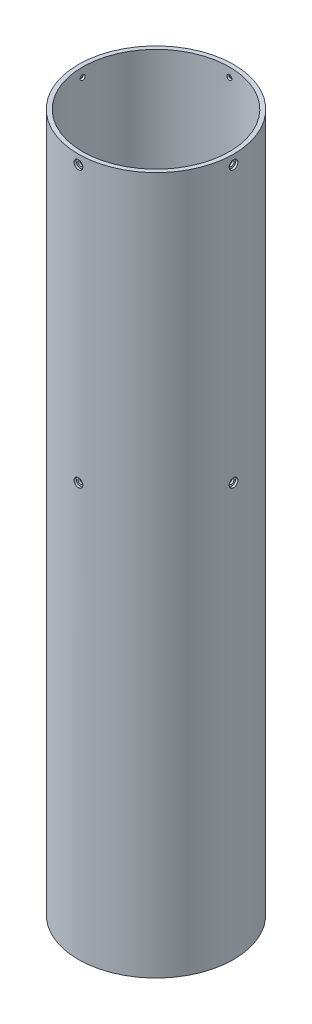
SolidWorks part; units mm, degrees
material "Hexcel AS4C (3000 Filaments)"
ref_plane "Front Plane" through (0, 0, 0) normal (0, 0, 1) x (1, 0, 0)
ref_plane "Top Plane" through (0, 0, 0) normal (0, 1, 0) x (1, 0, 0)
ref_plane "Right Plane" through (0, 0, 0) normal (1, 0, 0) x (0, 0, -1)
sketch "Sketch1" plane through (0, 0, 0) normal (0, 1, 0) x (1, 0, 0)
  circle A0 centre (0, 0) radius 50.8
  dimension "D1" = 101.6
extrude "Body Extrusion" add sketch "Sketch1" along normal blind 482.6 thin thin type one direction wall 2.921
ref_plane "Plane1" through (0, 0, 53.721) normal (0, 0, 1) x (1, 0, 0)
sketch "Sketch2" plane through (0, 0, 53.721) normal (0, 0, 1) x (1, 0, 0)
  line L0 (0, 482.6) -> (0, 0) construction
  line L1 (53.721, 482.6) -> (-53.721, 482.6) construction
  line L3 (50.8, 482.6) -> (-50.8, 482.6) construction
  circle A0 centre (0, 476.25) radius 1.7526
  dimension "D1" = 3.5052
  dimension "D2" = 6.35
extrude "Upper Bulkhead Holes" cut sketch "Sketch2" against normal up to next
pattern_circular "Upper Bulkhead Hole Pattern" count 4 over 360 about axis through (0, 482.6, 0) along (0, -1, 0) of "Upper Bulkhead Holes"
sketch "Sketch3" plane through (0, 0, 53.721) normal (0, 0, 1) x (1, 0, 0)
  line L0 (0, 482.6) -> (0, 0) construction
  line L1 (53.721, 482.6) -> (-53.721, 482.6) construction
  line L2 (50.8, 482.6) -> (-50.8, 482.6) construction
  circle A0 centre (0, 285.75) radius 1.7526
  dimension "D1" = 3.5052
  dimension "D2" = 285.75
  dimension "D3" = 196.85
extrude "Lower Bulkhead Holes" cut sketch "Sketch3" against normal up to next
pattern_circular "Lower Bulkhead Hole Pattern" count 4 over 360 about axis through (0, 482.6, 0) along (0, -1, 0) of "Lower Bulkhead Holes" reverse direction yes
sketch "Sketch4" plane through (0, 0, 53.721) normal (0, 0, 1) x (1, 0, 0)
  line L0 (0, 482.6) -> (0, 0) construction
  line L1 (50.8, 482.6) -> (-50.8, 482.6) construction
  line L2 (-50.8, 0) -> (50.8, 0) construction
  circle A0 centre (0, 476.25) radius 3.0226
  circle A1 centre (0, 285.75) radius 3.0226
  circle A2 centre (0, 285.75) radius 1.7526 construction
  circle A3 centre (0, 476.25) radius 1.7526 construction
  dimension "D1" = 1.27
  dimension "D2" = 1.27
extrude "Countersink" cut sketch "Sketch4" against normal blind 1.524
pattern_circular "Countersink Pattern" count 4 over 360 about axis through (0, 482.6, 0) along (0, -1, 0) of "Countersink"
equation "\"D2@Sketch4\"=\"D1@Sketch4\""
